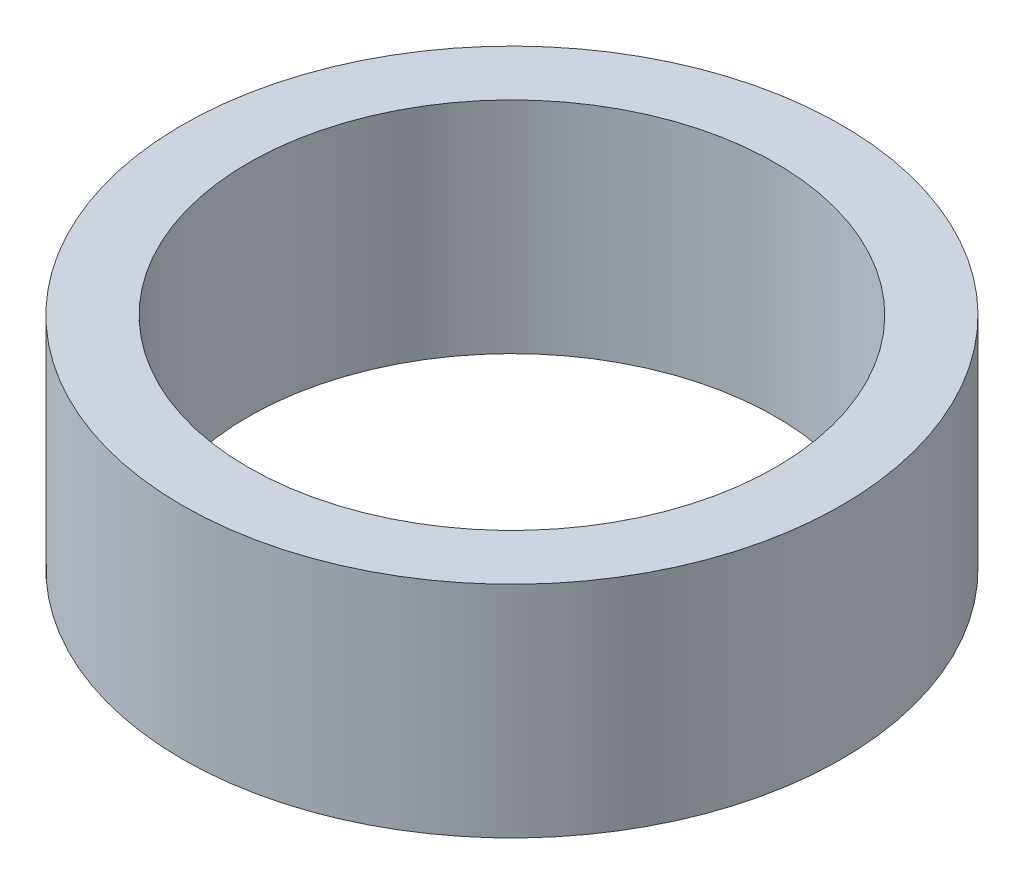
SolidWorks part; units mm, degrees
ref_plane "Front Plane" through (0, 0, 0) normal (0, 0, 1) x (1, 0, 0)
ref_plane "Top Plane" through (0, 0, 0) normal (0, 1, 0) x (1, 0, 0)
ref_plane "Right Plane" through (0, 0, 0) normal (1, 0, 0) x (0, 0, -1)
sketch "Sketch1" plane through (0, 0, 0) normal (0, 1, 0) x (1, 0, 0)
  circle A0 centre (0, 0) radius 37.5
  dimension "FLANGE_OD" = 75
extrude "Boss-Extrude1" add sketch "Sketch1" along normal blind 25
sketch "Sketch2" plane through (0, 0, 0) normal (0, 1, 0) x (1, 0, 0)
  circle A0 centre (0, 0) radius 30
  dimension "BORE_D" = 60
extrude "Cut-Extrude1" cut sketch "Sketch2" along normal through all
sketch "Sketch3" plane through (0, 25, 0) normal (0, 1, 0) x (1, 0, 0)
  circle A0 centre (0, 0) radius 16.3442 construction
  circle A1 centre (-16.3442, 0) radius 1.5
  dimension "BOLT_D" = 3
  dimension "BOLT_PCD" = 32.6884
extrude "Cut-Extrude2" cut sketch "Sketch3" against normal blind 17.0972 rebuild error yes
pattern_circular "CirPattern1" count 4 over 360 rebuild error yes
